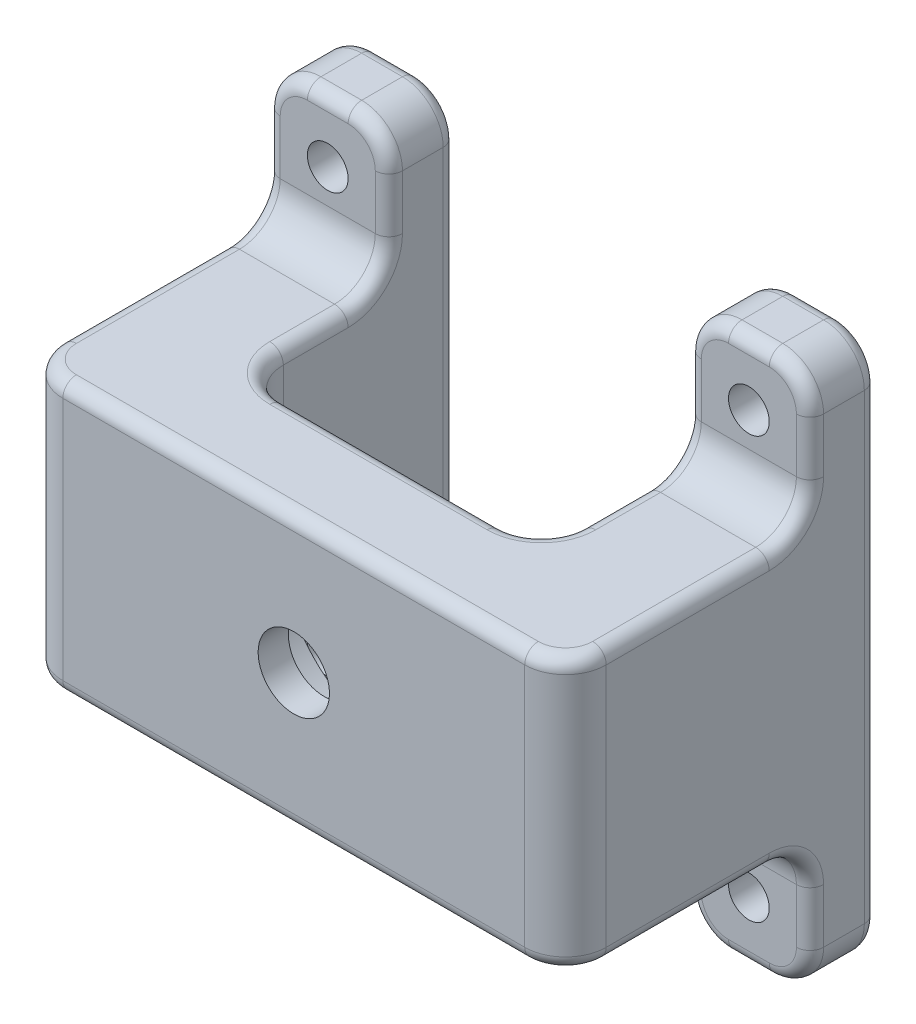
SolidWorks part; units mm, degrees
ref_plane "Front Plane" through (0, 0, 0) normal (0, 0, 1) x (1, 0, 0)
ref_plane "Top Plane" through (0, 0, 0) normal (0, 1, 0) x (1, 0, 0)
ref_plane "Right Plane" through (0, 0, 0) normal (1, 0, 0) x (0, 0, -1)
sketch "Sketch1" plane through (0, 0, 0) normal (0, 0, 1) x (1, 0, 0)
  line L1 (-20, 20) -> (20, 20)
  line L2 (-20, 20) -> (-20, -20)
  line L3 (-20, -20) -> (20, -20)
  line L4 (20, 20) -> (20, -20)
  line L5 (-20, 20) -> (20, -20) construction
  line L6 (-20, -20) -> (20, 20) construction
  point P0 (0, 0)
  dimension "D1" = 40
extrude "Boss-Extrude1" add sketch "Sketch1" along normal blind 23 contours L2 L3 L4 L1
sketch "Sketch2" plane through (0, -20, 0) normal (0, -1, 0) x (1, 0, 0)
  line L0 (-20, 0) -> (20, 0) construction
  line L1 (-11, 0) -> (11, 0)
  line L2 (-11, 0) -> (-11, 15.77)
  line L3 (-11, 15.77) -> (11, 15.77)
  line L4 (11, 0) -> (11, 15.77)
  point P6 (0, 15.77)
  dimension "D1" = 22
  dimension "D2" = 15.77
extrude "Cut-Extrude1" cut sketch "Sketch2" against normal through all
sketch "Sketch3" plane through (0, 0, 15.77) normal (0, 0, -1) x (-1, 0, 0)
  circle A0 centre (0, 0) radius 8
  dimension "D1" = 16
extrude "Cut-Extrude2" cut sketch "Sketch3" against normal blind 5
sketch "Sketch4" plane through (0, 0, 20.77) normal (0, 0, -1) x (-1, 0, 0)
  circle A0 centre (0, 0) radius 2.625
  dimension "D1" = 5.25
extrude "Cut-Extrude3" cut sketch "Sketch4" against normal through all
sketch "Sketch7" plane through (0, 0, 23) normal (0, 0, 1) x (1, 0, 0)
  line L1 (-15.5, -15.5) -> (15.5, -15.5) construction
  line L2 (-15.5, -15.5) -> (-15.5, 15.5) construction
  line L3 (-15.5, 15.5) -> (15.5, 15.5) construction
  line L4 (15.5, -15.5) -> (15.5, 15.5) construction
  line L5 (-15.5, -15.5) -> (15.5, 15.5) construction
  line L6 (-15.5, 15.5) -> (15.5, -15.5) construction
  circle A4 centre (-15.5, 15.5) radius 1.5
  circle A5 centre (15.5, 15.5) radius 1.5
  circle A6 centre (15.5, -15.5) radius 1.5
  circle A7 centre (-15.5, -15.5) radius 1.5
  point P0 (0, 0)
  dimension "D1" = 31
  dimension "D4" = 3
  dimension "D2" = 2
  dimension "D3" = 2
extrude "Cut-Extrude6" cut sketch "Sketch7" against normal through all
sketch "Sketch6" plane through (0, 0, 23) normal (0, 0, 1) x (1, 0, 0)
  line L0 (20, 20) -> (20, -20) construction
  line L5 (-20, -20) -> (20, -20)
  line L7 (-20, -20) -> (-20, -10)
  line L8 (-20, -10) -> (20, -10)
  line L17 (20, -20) -> (20, -10)
  line L19 (-20, 20) -> (20, 20)
  line L20 (-20, 20) -> (-20, 10)
  line L21 (-20, 10) -> (20, 10)
  line L22 (20, 20) -> (20, 10)
  dimension "D1" = 10
extrude "Cut-Extrude4" cut sketch "Sketch6" against normal offset from surface (18 mm away) 5 up to face at (17, -15.5, 0)
fillet "Fillet1" radius 3 16 edges at (-20, 0, 23) (20, 0, 23) (-20, 20, 2.5) (11, 20, 2.5) (-11, 20, 2.5) (20, 20, 2.5) (20, -20, 2.5) (11, -20, 2.5) (-20, -20, 2.5) (-11, -20, 2.5) (11, 0, 15.77) (-11, 0, 15.77) (-15.5, 10, 5) (15.5, 10, 5) (15.5, -10, 5) (-15.5, -10, 5)
fillet "Fillet2" radius 1 64 edges at (-11, -15, 5) (-11.8787, -19.1213, 5) (-15.5, -20, 5) (-19.1213, -19.1213, 5) (-11, 0, 0) (-11.8787, 19.1213, 0) (-15.5, 20, 0) (-19.1213, 19.1213, 0) (-11.8787, -19.1213, 0) (-15.5, -20, 0) (-19.1213, -19.1213, 0) (-11, 15, 5) (-11.8787, 19.1213, 5) (-15.5, 20, 5) (-19.1213, 19.1213, 5) (11, -15, 5) (11.8787, -19.1213, 5) (15.5, -20, 5) (19.1213, -19.1213, 5) (11, 15, 5) (11.8787, 19.1213, 5) (15.5, 20, 5) (19.1213, 19.1213, 5) (11, 0, 0) (11.8787, 19.1213, 0) (15.5, 20, 0) (19.1213, 19.1213, 0) (11.8787, -19.1213, 0) (15.5, -20, 0) (19.1213, -19.1213, 0) (-20, 10, 14) (-20, -10, 14) (-20, -15, 5) (-20, 0, 0) (-20, 15, 5) (20, -15, 5) (20, -10, 14) (20, 10, 14) (20, 15, 5) (20, 0, 0) (-11, 10, 10.385) (0, 10, 15.77) (11, 10, 10.385) (11, -10, 10.385) (0, -10, 15.77) (-11, -10, 10.385) (0, 10, 23) (0, -10, 23) (-10.1213, 10, 14.8913) (10.1213, 10, 14.8913) (10.1213, -10, 14.8913) (-10.1213, -10, 14.8913) (-19.1213, 10, 22.1213) (19.1213, 10, 22.1213) (19.1213, -10, 22.1213) (-19.1213, -10, 22.1213) (-11, 10.8787, 5.8787) (11, 10.8787, 5.8787) (11, -10.8787, 5.8787) (-11, -10.8787, 5.8787) (-20, -10.8787, 5.8787) (-20, 10.8787, 5.8787) (20, 10.8787, 5.8787) (20, -10.8787, 5.8787)
